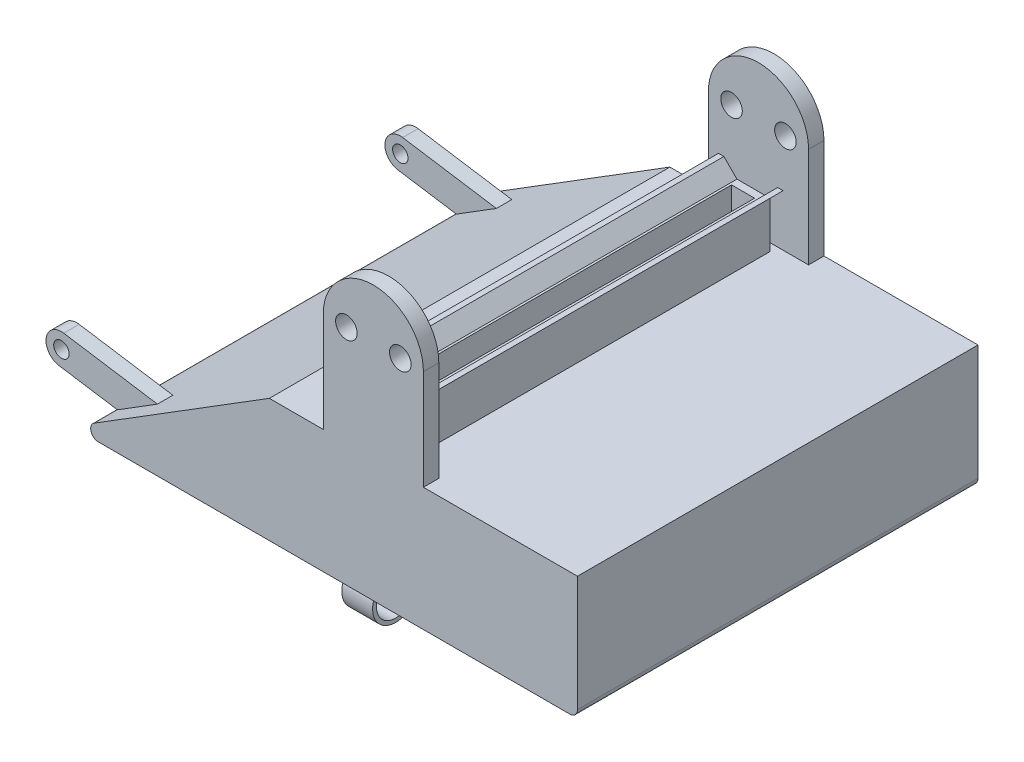
SolidWorks part; units mm, degrees
material "Nylon 101"
ref_plane "Front Plane" through (0, 0, 0) normal (0, 0, 1) x (1, 0, 0)
ref_plane "Top Plane" through (0, 0, 0) normal (0, 1, 0) x (1, 0, 0)
ref_plane "Right Plane" through (0, 0, 0) normal (1, 0, 0) x (0, 0, -1)
sketch "Sketch1" plane through (0, 0, 0) normal (0, 0, 1) x (1, 0, 0)
  circle A0 centre (0, 0) radius 15
  circle A2 centre (-200, -120) radius 10
  circle A3 centre (35, 0) radius 15
  dimension "D2" = 200
  dimension "D5" = 35
  dimension "D10" = 20
  dimension "D6" = 30
  dimension "D3" = 30
  dimension "D11" = 120
ref_plane "Plane1" through (0, -75, 0) normal (0, 1, 0) x (1, 0, 0)
sketch "Sketch5" plane through (0, -75, 0) normal (0, 1, 0) x (1, 0, 0)
  line L0 (-50, 125) -> (-50, -125)
  line L1 (-50, 125) -> (150, 125)
  line L3 (-50, -125) -> (150, -125)
  line L4 (150, 125) -> (150, -125)
  line L5 (10, 110) -> (25, 110)
  line L6 (10, 110) -> (10, -110)
  line L7 (10, -110) -> (25, -110)
  line L8 (25, 110) -> (25, -110)
  dimension "D1" = 50
  dimension "D2" = 250
  dimension "D3" = 125
  dimension "D4" = 15
  dimension "D5" = 10
  dimension "D6" = 110
  dimension "D7" = 220
  dimension "D8" = 200
extrude "Boss-Extrude7" add sketch "Sketch5" along normal blind 10 separate body
sketch "Sketch6" plane through (0, 0, 125) normal (0, 0, 1) x (1, 0, 0)
  line L0 (150, -75) -> (150, -140)
  line L1 (-160.9847, -145) -> (145, -145)
  line L2 (-50, -65) -> (-163.6276, -135.7556)
  line L3 (145, -135) -> (145, -75)
  line L4 (-50, -75) -> (150, -75) construction
  line L5 (-50, -65) -> (-50, -74.0036)
  line L7 (-55, -74.0036) -> (-50, -74.0036)
  line L8 (-55, -74.0036) -> (-153.5618, -135.3778)
  line L9 (-152.2403, -140) -> (140, -140)
  line L13 (145, -75) -> (150, -75)
  line L15 (-50, -65) -> (-50, -75) construction
  line L16 (-55, -74.0036) -> (-55, -75) construction
  line L17 (-178.4733, -145) -> (145, -145) construction
  line L18 (-50, -65) -> (-178.4733, -145) construction
  line L19 (-160.9847, -140) -> (135, -140) construction
  line L20 (-55, -74.0036) -> (-160.9847, -140) construction
  line L21 (135, -140) -> (135, -140) construction
  line L22 (135, -140) -> (135, -140) construction
  line L23 (135, -140) -> (135, -140) construction
  arc A0 (150, -140) -> (145, -145) centre (145, -140) cw
  arc A3 (-160.9847, -145) -> (-163.6276, -135.7556) centre (-160.9847, -140) cw
  arc A4 (145, -135) -> (140, -140) centre (140, -135) cw
  arc A5 (-152.2403, -140) -> (-153.5618, -135.3778) centre (-152.2403, -137.5) cw
  arc A8 (135, -140) -> (135, -140) centre (135, -140) cw construction
  arc A9 (135, -140) -> (135, -140) centre (135, -140) ccw construction
  point P10 (150, -145)
  point P15 (-178.4733, -145)
  point P37 (-178.4733, -145)
  dimension "D3" = 5
  dimension "D5" = 5
  dimension "D4" = 5
  dimension "D6" = 2.5
  dimension "D11" = 145
  dimension "D1" = 70
  dimension "D2" = 5
  dimension "D7" = 60
  dimension "D8" = 116.1087
  dimension "D9" = 133.8566
  dimension "D10" = 140
  dimension "D12" = 145
extrude "Boss-Extrude13" add sketch "Sketch6" against normal blind 250 separate body
sketch "Sketch7" plane through (0, 0, 125) normal (0, 0, 1) x (1, 0, 0)
  line L0 (150, -65) -> (-50, -65)
  line L1 (-50, -65) -> (150, -65) construction
  line L2 (-50, -65) -> (-163.6276, -135.7556)
  line L4 (-160.9847, -145) -> (145, -145)
  line L6 (150, -140) -> (150, -65)
  arc A0 (-163.6276, -135.7556) -> (-160.9847, -145) centre (-160.9847, -140) ccw
  arc A2 (145, -145) -> (150, -140) centre (145, -140) ccw
extrude "Boss-Extrude14" add sketch "Sketch7" along normal blind 5
mirror "Mirror1" about plane through (0, 0, 0) normal (0, 0, 1) of "Boss-Extrude14"
sketch "Sketch8" plane through (0, -65, 0) normal (0, 1, 0) x (1, 0, 0)
  line L0 (5, 115) -> (30, 115)
  line L1 (10, 110) -> (25, 110)
  line L2 (10, 110) -> (10, -110)
  line L3 (10, -110) -> (25, -110)
  line L4 (25, 110) -> (25, -110)
  line L5 (30, 115) -> (30, -115)
  line L6 (5, -115) -> (30, -115)
  line L7 (5, 115) -> (5, -115)
  dimension "D1" = 5
extrude "Boss-Extrude15" add sketch "Sketch8" along normal blind 30
sketch "Sketch9" plane through (0, 0, 115) normal (0, 0, 1) x (1, 0, 0)
  line L1 (30, -35) -> (38.4853, -26.5147)
  line L2 (5, -35) -> (-3.4853, -26.5147)
  line L3 (5, -31.4645) -> (0.0503, -26.5147)
  line L5 (30, -31.4645) -> (34.9497, -26.5147)
  line L6 (-3.4853, -26.5147) -> (0.0503, -26.5147)
  line L7 (6.0355, -32.5) -> (-1.7175, -24.747) construction
  line L8 (28.9645, -32.5) -> (36.7175, -24.747) construction
  line L9 (34.9497, -26.5147) -> (38.4853, -26.5147)
  line L10 (6.0355, -32.5) -> (28.9645, -32.5) construction
  line L11 (5, -35) -> (30, -35) construction
  line L12 (5, -31.4645) -> (8.5355, -35)
  line L13 (5, -35) -> (30, -35) construction
  line L14 (30, -31.4645) -> (26.4645, -35)
  line L15 (5, -35) -> (8.5355, -35)
  line L16 (30, -35) -> (26.4645, -35)
  dimension "D1" = 12
  dimension "D2" = 12
  dimension "D3" = 2.5
extrude "Boss-Extrude16" add sketch "Sketch9" against normal up to surface (230 mm away) up to face at (17.5, -50, -115)
sketch "Sketch11" plane through (0, 0, 130) normal (0, 0, 1) x (1, 0, 0)
  line L0 (-15, -65) -> (50, -65)
  line L1 (150, -65) -> (-50, -65) construction
  line L2 (50, -65) -> (50, 0)
  line L4 (-15, 0) -> (-15, -65)
  arc A2 (50, 0) -> (-15, 0) centre (17.5, 0) ccw
  circle A3 centre (0, 0) radius 7
  circle A4 centre (35, 0) radius 7
  dimension "D1" = 32.5
  dimension "D2" = 14
  dimension "D3" = 14
  dimension "D6" = 32.5
  dimension "D4" = 65
  dimension "D5" = 35
  dimension "D7" = 15
  dimension "D8" = 15
extrude "Boss-Extrude17" add sketch "Sketch11" against normal blind 10
mirror "Mirror2" about plane through (0, 0, 0) normal (0, 0, 1) of "Boss-Extrude17"
ref_plane "Plane2" through (0, 0, 115) normal (0, 0, 1) x (1, 0, 0)
sketch "Sketch12" plane through (0, 0, 115) normal (0, 0, 1) x (1, 0, 0)
  line L0 (-198.4644, -110.1186) -> (-137.6371, -119.5714)
  line L2 (-50, -65) -> (-163.6276, -135.7556) construction
  line L3 (-201.5313, -129.8821) -> (-163.6276, -135.7556)
  line L4 (-163.6276, -135.7556) -> (-137.6371, -119.5714)
  arc A2 (-198.4644, -110.1186) -> (-201.5313, -129.8821) centre (-200, -120) ccw
  circle A3 centre (-200, -120) radius 5
  dimension "D1" = 60.8273
  dimension "D3" = 10
  dimension "D2" = 9.4528
  dimension "D4" = 37.9037
  dimension "D5" = 5.8736
extrude "Boss-Extrude18" add sketch "Sketch12" against normal blind 10
mirror "Mirror3" about plane through (0, 0, 0) normal (0, 0, 1) of "Boss-Extrude18"
ref_plane "Plane3" through (-7.9923, 0, 0) normal (1, 0, 0) x (0, 0, -1)
ref_axis "Axis2" through (0, 0, 120) along (0, 0, 1)
ref_axis "Axis3" through (35, 0, 120) along (0, 0, 1)
ref_axis "Axis4" through (-200, -120, 105) along (0, 0, 1)
sketch "Sketch14" plane through (-7.9923, 0, 0) normal (1, 0, 0) x (0, 0, -1)
  line L0 (-110, -145) -> (-110, -153.8197)
  line L2 (-130, -145) -> (130, -145) construction
  line L3 (-110, -145) -> (-90, -145)
  line L5 (-90, -153.8197) -> (-90, -145)
  arc A0 (-110, -153.8197) -> (-90, -153.8197) centre (-100, -165) ccw
  circle A1 centre (-100, -165) radius 12.5
  dimension "D1" = 30
  dimension "D2" = 25
extrude "Boss-Extrude20" add sketch "Sketch14" against normal mid plane 20 separate body
mirror "Mirror11" about plane through (0, 0, 0) normal (0, 0, 1) of "Boss-Extrude20"
sketch "Sketch18" plane through (0, 0, 0) normal (0, 0, 1) x (1, 0, 0)
  line L1 (-160.9847, -145) -> (145, -145) construction
  line L2 (-117.9947, -145) -> (-97.9947, -145)
  line L3 (-117.9947, -145) -> (-117.9947, -153.8197)
  line L5 (-97.9947, -153.8197) -> (-97.9947, -145)
  circle A1 centre (-107.9947, -165) radius 12.5
  arc A2 (-117.9947, -153.8197) -> (-97.9947, -153.8197) centre (-107.9947, -165) ccw
  point P0 (-107.9947, -145)
  dimension "D3" = 25
  dimension "D5" = 30
  dimension "D1" = 42.99
  dimension "D2" = 20
  dimension "D4" = 20
extrude "Boss-Extrude21" add sketch "Sketch18" along normal mid plane 20
mirror "Mirror15" about plane through (-7.9923, 0, 0) normal (1, 0, 0) of "Boss-Extrude21"
ref_axis "T1" through (-107.9947, -165, 10) along (0, 0, -1)
ref_axis "T2" through (-17.9923, -165, 100) along (1, 0, 0)
ref_axis "T3" through (92.01, -165, 10) along (0, 0, -1)
ref_axis "T4" through (-17.9923, -165, -100) along (1, 0, 0)
